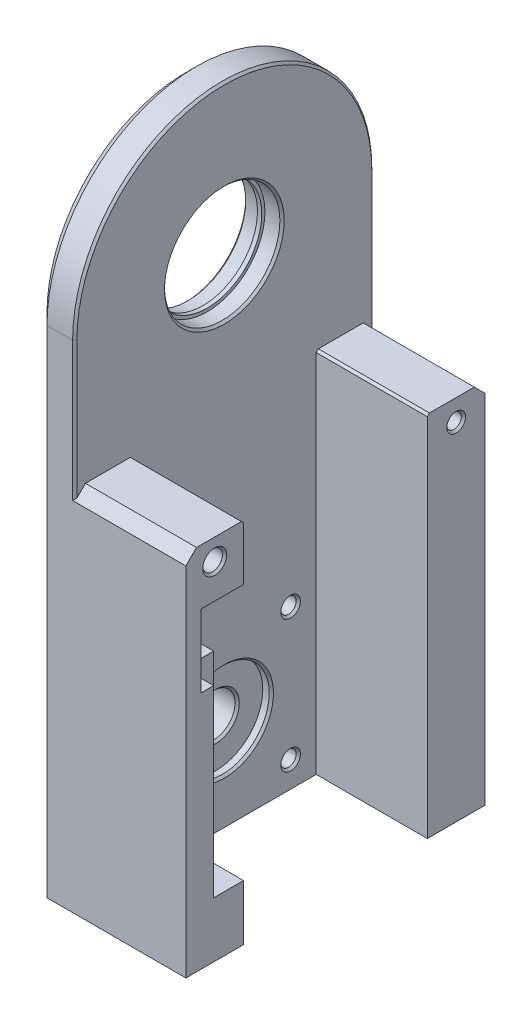
SolidWorks part; units mm, degrees
note: The reader was unsure of these and kept them because the rebuilt part matched: shared geometry of "Sketch2<3>", "Sketch3<3>", "Sketch3<4>".
ref_plane "Ebene vorne" through (0, 0, 0) normal (0, 0, 1) x (1, 0, 0)
ref_plane "Ebene oben" through (0, 0, 0) normal (0, 1, 0) x (1, 0, 0)
ref_plane "Ebene rechts" through (0, 0, 0) normal (1, 0, 0) x (0, 0, -1)
sketch "Sketch2" plane through (0, 0, 0) normal (1, 0, 0) x (0, 0, -1)
  line L1 (0, 0) -> (70, 0)
  line L2 (0, 0) -> (0, 86)
  line L3 (0, 86) -> (70, 86)
  line L4 (70, 0) -> (70, 86)
  line L5 (0, 0) -> (70, 86) construction
  line L6 (0, 86) -> (70, 0) construction
  line L7 (0, 86) -> (70, 86)
  line L8 (0, 86) -> (0, 116)
  line L9 (0, 116) -> (70, 116)
  line L10 (70, 86) -> (70, 116)
  line L11 (0, 86) -> (70, 116) construction
  line L12 (0, 116) -> (70, 86) construction
  circle A0 centre (35, 116) radius 35
  circle A1 centre (35, 116) radius 12.75
  point P4 (35, 43)
  point P9 (35, 101)
  point P13 (0, 0)
  point P14 (0, 116)
  point P15 (0, 116)
  point P16 (-0.5, 116)
  point P17 (70, 116)
  dimension "D4" = 70
  dimension "D5" = 25.5
  dimension "D2" = 86
  dimension "D3" = 30
extrude "Boss-Extrude1" add sketch "Sketch2" along normal blind 35 contours A0 L3 L2 L1 L4 | L7 A0
sketch "Sketch3" plane through (35, 0, 0) normal (1, 0, 0) x (0, 0, -1)
  line L1 (0, 86) -> (70, 86) construction
  line L2 (0, 0) -> (70, 0) construction
  line L8 (35, 0) -> (35, 86) construction
  line L9 (13.5, 0) -> (56.5, 0)
  line L10 (13.5, 0) -> (13.5, 43)
  line L11 (13.5, 43) -> (56.5, 43)
  line L12 (56.5, 0) -> (56.5, 43)
  line L13 (13.5, 0) -> (56.5, 43) construction
  line L14 (13.5, 43) -> (56.5, 0) construction
  line L15 (56.5, 43) -> (13.5, 43)
  line L16 (56.5, 43) -> (56.5, 86)
  line L17 (56.5, 86) -> (13.5, 86)
  line L18 (13.5, 43) -> (13.5, 86)
  line L19 (56.5, 43) -> (13.5, 86) construction
  line L20 (56.5, 86) -> (13.5, 43) construction
  line L21 (13.5, 73) -> (3.5, 73)
  line L22 (13.5, 73) -> (13.5, 56)
  line L23 (13.5, 56) -> (3.5, 56)
  line L24 (3.5, 73) -> (3.5, 56)
  line L25 (13.5, 73) -> (3.5, 56) construction
  line L26 (13.5, 56) -> (3.5, 73) construction
  circle A0 centre (35, 21.5) radius 11
  circle A1 centre (35, 21.5) radius 5
  point P10 (0, 0)
  point P15 (35, 21.5)
  point P19 (35, 64.5)
  point P26 (8.5, 64.5)
  dimension "D3" = 22
  dimension "D4" = 10
  dimension "D5" = 10
  dimension "D6" = 17
extrude "Cut-Extrude1" cut sketch "Sketch3" against normal offset from surface (26 mm away) 9
extrude "Boss-Extrude2" add sketch "Sketch2<3>" along normal up to surface (9 mm away) contours L9 A0 L7 | A0 L3 L10 | A0 L8 L3 | L9 A0 up to face at (9, 53.75, -21.75)
sketch "Sketch2<3>" plane through (0, 0, 0) normal (1, 0, 0) x (0, 0, -1) same geometry as "Sketch2"
extrude "Cut-Extrude2" cut sketch "Sketch3<3>" against normal offset from surface (28 mm away) 2 contours A0 A1 | A1 up to face at (9, 72.4167, -26.1667) offset beyond the face yes
sketch "Sketch3<3>" plane through (35, 0, 0) normal (1, 0, 0) x (0, 0, -1) same geometry as "Sketch3"
extrude "Cut-Extrude3" cut sketch "Sketch3<4>" against normal through all contours A1
sketch "Sketch3<4>" plane through (35, 0, 0) normal (1, 0, 0) x (0, 0, -1) same geometry as "Sketch3"
sketch "Sketch15" plane through (9, 0, 0) normal (1, 0, 0) x (0, 0, -1)
  circle A0 centre (35, 116) radius 13.5
  dimension "D1" = 27
extrude "Cut-Extrude4" cut sketch "Sketch15" against normal blind 4
ref_plane "Plane1" through (4.5, 0, 0) normal (1, 0, 0) x (0, 0, -1)
mirror "Mirror1" about plane through (4.5, 0, 0) normal (1, 0, 0) of "Cut-Extrude4"
hole_wizard "CBORE for M3 Hex Socket Head Cap Screw1" positions "Sketch4" profile "Sketch5" counterbore size "M3" standard "DIN" end condition through all
sketch "Sketch4" plane through (0, 0, 0) normal (-1, 0, 0) x (0, 0, 1)
  line L1 (-50.5, 6) -> (-19.5, 6)
  line L2 (-50.5, 6) -> (-50.5, 37)
  line L3 (-50.5, 37) -> (-19.5, 37)
  line L4 (-19.5, 6) -> (-19.5, 37)
  line L5 (-50.5, 6) -> (-19.5, 37) construction
  line L6 (-50.5, 37) -> (-19.5, 6) construction
  point P0 (-35, 21.5)
  point P1 (-19.5, 37)
  point P4 (-50.5, 6)
  point P5 (-50.5, 37)
  point P6 (-19.5, 6)
  dimension "D1" = 31
sketch "Sketch5" plane through (0, 6, -19.5) normal (0, 1, 0) x (0, 0, 1)
  line L0 (0, 0) -> (0, 35)
  line L1 (0, 35) -> (1.8, 35)
  line L3 (1.8, 35) -> (1.8, 3.4)
  line L4 (1.8, 3.4) -> (3.25, 3.4)
  line L5 (3.25, 3.4) -> (3.25, 0)
  line L7 (3.25, 0) -> (0, 0)
  line L11 (0, -6.35) -> (0, 107.95) construction
  dimension "Thru Hole Dia." = 3.6
  dimension "Thru Hole Depth" = 35
  dimension "C'Bore Dia." = 6.5
  dimension "C'Bore Depth" = 3.4
hole_wizard "Ø4.6 (4.6) Diameter Hole1" positions "Sketch8" profile "Sketch9" hole size "Ø4.6" standard "DIN"
sketch "Sketch8" plane through (0, 0, 0) normal (0, -1, 0) x (-1, 0, 0)
  line L0 (-35, 70) -> (-35, 0) construction
  line L1 (-35, 0) -> (0, 0) construction
  line L2 (-35, 0) -> (-35, 13.5) construction
  line L5 (-65.5, 6.5) -> (-4.5, 6.5)
  line L6 (-65.5, 6.5) -> (-65.5, 63.5)
  line L7 (-65.5, 63.5) -> (-4.5, 63.5)
  line L8 (-4.5, 6.5) -> (-4.5, 63.5)
  line L9 (-65.5, 6.5) -> (-4.5, 63.5) construction
  line L10 (-65.5, 63.5) -> (-4.5, 6.5) construction
  line L11 (-35, 70) -> (0, 70) construction
  line L12 (0, 0) -> (0, 70) construction
  point P9 (-35, 35)
  point P10 (-4.5, 63.5)
  point P15 (-4.5, 6.5)
  point P89 (-4.5, 35)
  dimension "D1" = 6.5
  dimension "D2" = 4.5
sketch "Sketch9" plane through (4.5, 0, -35) normal (1, 0, 0) x (0, 0, -1)
  line L0 (0, 0) -> (0, 7.382)
  line L1 (0, 7.382) -> (2.3, 6)
  line L2 (2.3, 6) -> (2.3, 0)
  line L5 (2.3, 0) -> (0, 0)
  line L10 (0, 7.382) -> (-2.3, 6) construction
  line L11 (0, -6.35) -> (0, 107.95) construction
  dimension "Hole Dia." = 4.6
  dimension "Hole Depth" = 6
  dimension "Drill Angle" = 118
hole_wizard "CBORE for M3 Hex Socket Head Cap Screw2" positions "Sketch10" profile "Sketch11" counterbore size "M3" standard "DIN" end condition through all
sketch "Sketch10" plane through (0, 0, 0) normal (-1, 0, 0) x (0, 0, 1)
  line L0 (-56.5, 86) -> (-70, 86) construction
  line L1 (-56.5, 86) -> (-70, 86)
  line L2 (-63.25, 86) -> (-63.25, 81) construction
  point P4 (-63.25, 81)
  dimension "D1" = 5
sketch "Sketch11" plane through (0, 81, -63.25) normal (0, 1, 0) x (0, 0, 1)
  line L0 (0, 0) -> (0, 35)
  line L1 (0, 35) -> (1.7, 35)
  line L3 (1.7, 35) -> (1.7, 3.4)
  line L4 (1.7, 3.4) -> (3.25, 3.4)
  line L5 (3.25, 3.4) -> (3.25, 0)
  line L7 (3.25, 0) -> (0, 0)
  line L11 (0, -6.35) -> (0, 107.95) construction
  dimension "Thru Hole Dia." = 3.4
  dimension "Thru Hole Depth" = 35
  dimension "C'Bore Dia." = 6.5
  dimension "C'Bore Depth" = 3.4
hole_wizard "Ø4.6 (4.6) Diameter Hole2" positions "Sketch12" profile "Sketch14" hole size "Ø4.6" standard "DIN"
sketch "Sketch12" plane through (35, 0, 0) normal (1, 0, 0) x (0, 0, -1)
  line L0 (6.75, 86) -> (6.75, 81) construction
  line L1 (0, 86) -> (13.5, 86) construction
  point P1 (6.75, 81)
  dimension "D1" = 5
sketch "Sketch14" plane through (35, 81, -6.75) normal (0, 1, 0) x (0, 0, -1)
  line L0 (0, 0) -> (0, 7.382)
  line L1 (0, 7.382) -> (2.3, 6)
  line L2 (2.3, 6) -> (2.3, 0)
  line L5 (2.3, 0) -> (0, 0)
  line L10 (0, 7.382) -> (-2.3, 6) construction
  line L11 (0, -6.35) -> (0, 107.95) construction
  dimension "Hole Dia." = 4.6
  dimension "Hole Depth" = 6
  dimension "Drill Angle" = 118
hole_wizard "Ø4.6 (4.6) Diameter Hole3" positions "Sketch18" profile "Sketch17" hole size "Ø4.6" standard "DIN"
sketch "Sketch18" plane through (0, 0, 0) normal (-1, 0, 0) x (0, 0, 1)
  line L0 (-35, 21.5) -> (-35, 116) construction
  point P9 (-10, 68.75)
  point P18 (-35, 68.75)
  point P20 (-60, 68.75)
  dimension "D1" = 25
sketch "Sketch17" plane through (0, 68.75, -60) normal (0, 1, 0) x (0, 0, 1)
  line L0 (0, 0) -> (0, 6.382)
  line L1 (0, 6.382) -> (2.3, 5)
  line L2 (2.3, 5) -> (2.3, 0)
  line L5 (2.3, 0) -> (0, 0)
  line L10 (0, 6.382) -> (-2.3, 5) construction
  line L11 (0, -6.35) -> (0, 107.95) construction
  dimension "Hole Dia." = 4.6
  dimension "Hole Depth" = 5
  dimension "Drill Angle" = 118
sketch "Sketch19" plane through (0, 0, -13.5) normal (0, 0, -1) x (-1, 0, 0)
  line L1 (-35, 56) -> (-28, 56)
  line L2 (-35, 56) -> (-35, 13)
  line L3 (-35, 13) -> (-28, 13)
  line L4 (-28, 56) -> (-28, 13)
  line L5 (-35, 56) -> (-28, 13) construction
  line L6 (-35, 13) -> (-28, 56) construction
  point P4 (-31.5, 34.5)
  dimension "D1" = 7
  dimension "D2" = 43
extrude "Cut-Extrude5" cut sketch "Sketch19" against normal blind 7
chamfer "2,5mm Chamfer1" distance 2.5 angle 45 5 edges at (22, 86, -70) (22, 86, 0) (0, 58, 0) (0, 151, -35) (0, 58, -70)
chamfer "0,5mm Chamfer2" distance 0.5 angle 45 26 edges at (0, 21.5, -40) (7, 21.5, -40) (9, 21.5, -46) (4.5, 0, -8.8) (4.5, 0, -37.3) (4.5, 0, -65.8) (9, 6, -21.3) (9, 6, -52.3) (9, 37, -52.3) (9, 37, -21.3) (35, 81, -61.55) (35, 81, -9.05) (9, 99.75, -70) (9, 99.75, 0) (9, 151, -35) (0, 6, -16.25) (0, 6, -47.25) (0, 37, -16.25) (0, 37, -47.25) (0, 81, -60) (22, 86, -56.5) (0, 116, -48.5) (9, 116, -48.5) (0, 68.75, -7.7) (0, 68.75, -57.7) (22, 86, -13.5)
